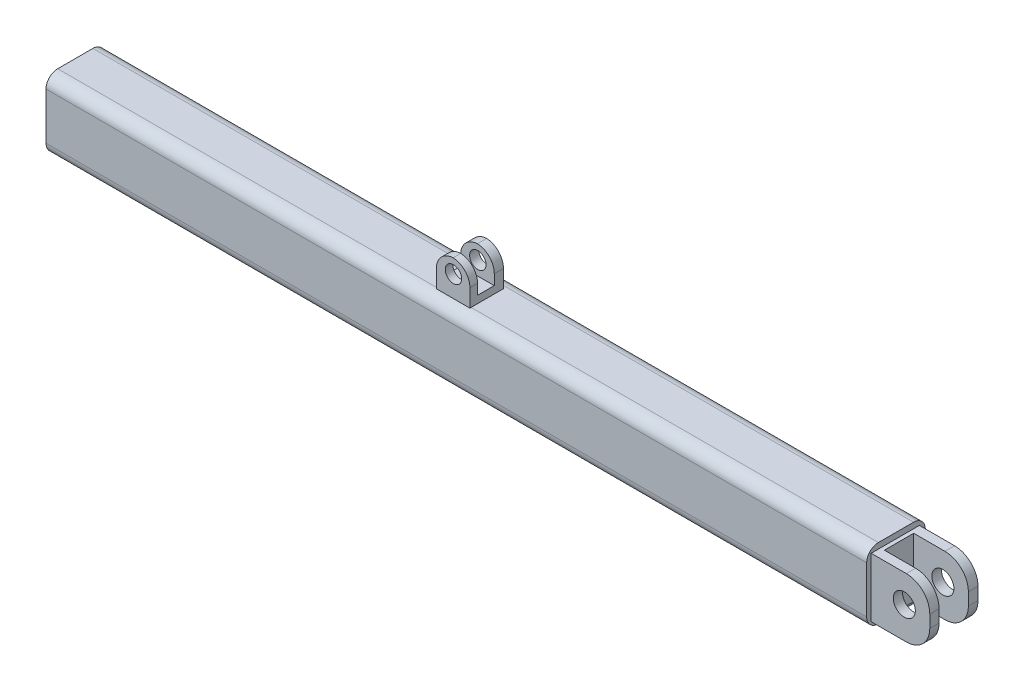
SolidWorks part; units mm, degrees
ref_plane "Front Plane" through (0, 0, 0) normal (0, 0, 1) x (1, 0, 0)
ref_plane "Top Plane" through (0, 0, 0) normal (0, 1, 0) x (1, 0, 0)
ref_plane "Right Plane" through (0, 0, 0) normal (1, 0, 0) x (0, 0, -1)
sketch "Sketch1" plane through (0, 0, 0) normal (0, 0, 1) x (1, 0, 0)
  line L1 (-35, 3) -> (35, 3)
  line L2 (-35, 3) -> (-35, -3)
  line L3 (-35, -3) -> (35, -3)
  line L4 (35, 3) -> (35, -3)
  line L5 (-35, 3) -> (35, -3) construction
  line L6 (-35, -3) -> (35, 3) construction
  point P0 (0, 0)
  dimension "D1" = 70
  dimension "D2" = 6
extrude "Boss-Extrude1" add sketch "Sketch1" along normal blind 5
sketch "Sketch5" plane through (0, 0, 0) normal (1, 0, 0) x (0, 0, -1)
  line L1 (-4.6176, -2.5388) -> (-0.5041, -2.5388)
  line L2 (-4.6176, -2.5388) -> (-4.6176, 2.5154)
  line L3 (-4.6176, 2.5154) -> (-0.5041, 2.5154)
  line L4 (-0.5041, -2.5388) -> (-0.5041, 2.5154)
  line L5 (-4.6176, -2.5388) -> (-0.5041, 2.5154) construction
  line L6 (-4.6176, 2.5154) -> (-0.5041, -2.5388) construction
  point P0 (-2.5608, -0.0117)
extrude "Boss-Extrude4" add sketch "Sketch5" along normal blind 40
sketch "Sketch9" plane through (0, -2.5388, 0) normal (0, -1, 0) x (1, 0, 0)
  line L1 (35.3355, 3.8247) -> (40.5244, 3.8247)
  line L2 (35.3355, 3.8247) -> (35.3355, 1.3261)
  line L3 (35.3355, 1.3261) -> (40.5244, 1.3261)
  line L4 (40.5244, 3.8247) -> (40.5244, 1.3261)
  line L5 (35.3355, 3.8247) -> (40.5244, 1.3261) construction
  line L6 (35.3355, 1.3261) -> (40.5244, 3.8247) construction
  point P4 (37.9299, 2.5754)
extrude "Cut-Extrude6" cut sketch "Sketch9" against normal blind 6
fillet "Fillet14" radius 1 1 edges at (0, 3, 5)
fillet "Fillet15" radius 1 3 edges at (0, -3, 5) (0, -3, 0) (0, 3, 0)
sketch "Sketch11" plane through (0, 0, 0.5041) normal (0, 0, -1) x (-1, 0, 0)
  circle A0 centre (-37.8269, 0.145) radius 0.9395
extrude "Cut-Extrude8" cut sketch "Sketch11" against normal blind 6
fillet "Fillet19" radius 2 4 edges at (40, -2.5388, 0.9151) (40, -2.5388, 4.2211) (40, 2.5154, 4.2211) (40, 2.5154, 0.9151)
sketch "Sketch12" plane through (0, 0, 0) normal (0, 1, 0) x (1, 0, 0)
  line L1 (0.2605, -1.2421) -> (-2.605, -1.2421)
  line L2 (0.2605, -1.2421) -> (0.2605, -4.1013)
  line L3 (0.2605, -4.1013) -> (-2.605, -4.1013)
  line L4 (-2.605, -1.2421) -> (-2.605, -4.1013)
  line L5 (0.2605, -1.2421) -> (-2.605, -4.1013) construction
  line L6 (0.2605, -4.1013) -> (-2.605, -1.2421) construction
  point P4 (-1.1723, -2.6717)
extrude "Boss-Extrude5" add sketch "Sketch12" along normal blind 6
sketch "Sketch13" plane through (0, 0, 0) normal (1, 0, 0) x (0, 0, -1)
  line L1 (-2.0256, 3.619) -> (-3.4504, 3.619)
  line L2 (-2.0256, 3.619) -> (-2.0256, 6.2558)
  line L3 (-2.0256, 6.2558) -> (-3.4504, 6.2558)
  line L4 (-3.4504, 3.619) -> (-3.4504, 6.2558)
  line L5 (-2.0256, 3.619) -> (-3.4504, 6.2558) construction
  line L6 (-2.0256, 6.2558) -> (-3.4504, 3.619) construction
  point P4 (-2.738, 4.9374)
extrude "Cut-Extrude9" cut sketch "Sketch13" against normal blind 5 and the other way blind 12 contours L1 L4 L3 L2
sketch "Sketch14" plane through (0, 0, 0) normal (0, 0, 1) x (1, 0, 0)
  circle A0 centre (-1.1417, 4.8047) radius 0.7
  point P2 (-0.9081, 4.6106)
  point P3 (-1.1417, 4.8047)
  dimension "D1" = 1.4
extrude "Cut-Extrude10" cut sketch "Sketch14" along normal blind 13
fillet "Fillet20" radius 1.5 4 edges at (0.2605, 6, 3.7759) (0.2605, 6, 1.6338) (-2.605, 6, 3.7759) (-2.605, 6, 1.6338)
